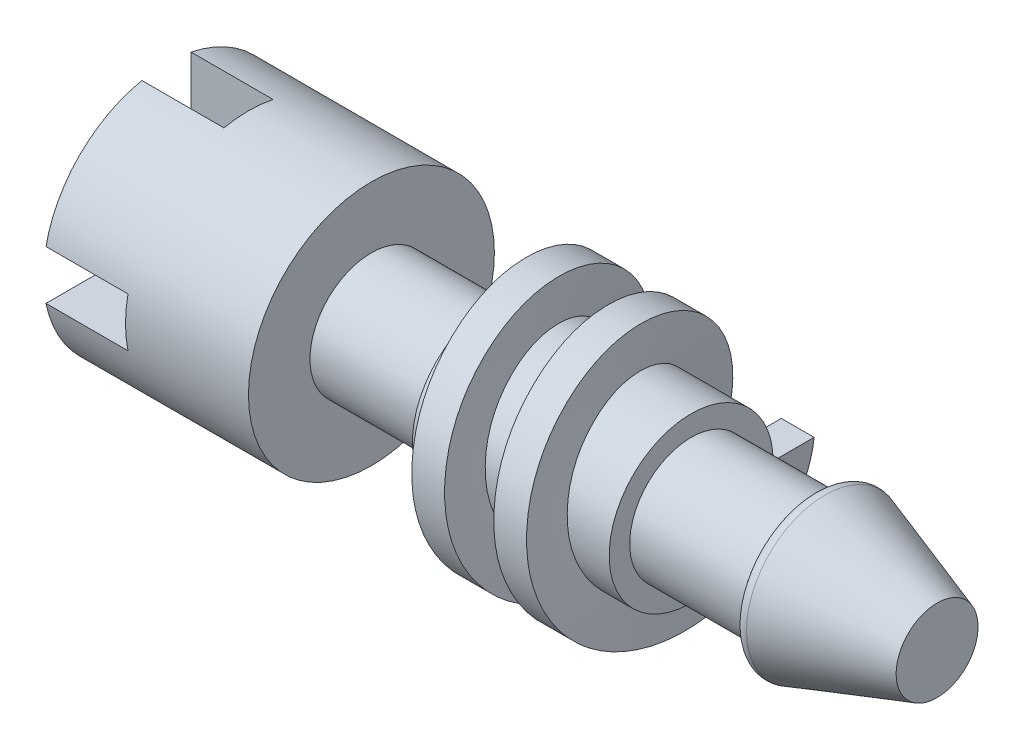
SolidWorks part; units mm, degrees
material "AISI 304"
ref_plane "Front Plane" through (0, 0, 0) normal (0, 0, 1) x (1, 0, 0)
ref_plane "Top Plane" through (0, 0, 0) normal (0, 1, 0) x (1, 0, 0)
ref_plane "Right Plane" through (0, 0, 0) normal (1, 0, 0) x (0, 0, -1)
sketch "Sketch1" plane through (0, 0, 0) normal (1, 0, 0) x (0, 0, -1)
  circle A0 centre (0, 0) radius 1.5
  circle A1 centre (0, 0) radius 1
  circle A2 centre (0, 0) radius 0.75
  dimension "D1" = 2
  dimension "D2" = 3
  dimension "D3" = 1.5
extrude "Boss-Extrude4" add sketch "Sketch1" along normal blind 1.5 contours A2
extrude "Boss-Extrude5" add sketch "Sketch1<6>" against normal blind 2.5 contours A0
sketch "Sketch1<6>" plane through (0, 0, 0) normal (1, 0, 0) x (0, 0, -1) same geometry as "Sketch1"
extrude "Boss-Extrude6" add sketch "Sketch1<7>" along normal blind 2.4 from surface contours A1 starting at face at (1.5, 0, -0.75)
sketch "Sketch1<7>" plane through (0, 0, 0) normal (1, 0, 0) x (0, 0, -1) same geometry as "Sketch1"
ref_plane "Plane2" through (1.75, 0, 0) normal (-1, 0, 0) x (0, 0, 1)
sketch "Sketch6" plane through (1.75, 0, 0) normal (-1, 0, 0) x (0, 0, 1)
  circle A0 centre (0, 0) radius 1.5
  dimension "D1" = 3
curve "Helix/Spiral2" pitch 1 height 2 radius 1.5 centre (1.75, 0, 0) axis (1, 0, 0) start towards (0, 0, 1)
sketch "Sketch7" plane through (0, 0, 0) normal (0, 1, 0) x (1, 0, 0)
  line L0 (3.9, 1) -> (1.5, 1) construction
  line L1 (1.5, 1.5) -> (1.9, 1.5)
  line L2 (1.5, 1.5) -> (1.5, 1)
  line L3 (1.5, 1) -> (1.9, 1)
  line L4 (1.9, 1.5) -> (1.9, 1)
  line L5 (0, -1.5) -> (0, 1.5) construction
  point P6 (1.7, 1.5)
  dimension "D1" = 0.4
  dimension "D2" = 0.5
  dimension "D3" = 1.7
sweep "Sweep2" add profiles "Sketch7" path "Helix/Spiral2"
extrude "Boss-Extrude7" add sketch "Sketch1<8>" along normal blind 1.5 from surface contours A2 starting at face at (3.9, 0, -1)
sketch "Sketch1<8>" plane through (0, 0, 0) normal (1, 0, 0) x (0, 0, -1) same geometry as "Sketch1"
sketch "Sketch8" plane through (-2.5, 0, 0) normal (-1, 0, 0) x (0, 0, 1)
  line L0 (0, 1.5) -> (0, -1.5) construction
  line L1 (-1.5, 0) -> (1.5, 0) construction
  line L2 (0.3, 1.4697) -> (0.3, 0.3)
  line L3 (-1.4697, 0.3) -> (-0.3, 0.3)
  line L4 (-0.3, 1.4697) -> (-0.3, 0.3)
  line L5 (-1.4697, -0.3) -> (-0.3, -0.3)
  line L6 (0.3, 0.3) -> (1.4697, 0.3)
  line L7 (-0.3, -0.3) -> (-0.3, -1.4697)
  line L8 (0.3, -0.3) -> (0.3, -1.4697)
  line L9 (0.3, -0.3) -> (1.4697, -0.3)
  circle A0 centre (0, 0) radius 1.5 construction
  arc A1 (-1.4697, 0.3) -> (-1.4697, -0.3) centre (0, 0) ccw
  arc A2 (0.3, 1.4697) -> (-0.3, 1.4697) centre (0, 0) ccw
  arc A3 (1.4697, -0.3) -> (1.4697, 0.3) centre (0, 0) ccw
  arc A4 (-0.3, -1.4697) -> (0.3, -1.4697) centre (0, 0) ccw
  dimension "D1" = 0.3
  dimension "D2" = 0.3
extrude "Cut-Extrude2" cut sketch "Sketch8" against normal blind 1
sketch "Sketch9" plane through (0, 0, 0) normal (0, 1, 0) x (1, 0, 0)
  line L0 (0, 0) -> (7.4883, 0) construction
  line L1 (5.4, 0) -> (5.4, 1)
  line L2 (5.4, -0.75) -> (5.4, 0.75) construction
  line L3 (5.4, 1) -> (6.9, 0.5)
  line L4 (6.9, 0.5) -> (6.9, 0)
  line L5 (5.4, 0) -> (6.9, 0)
  dimension "D1" = 1
  dimension "D2" = 1.5
  dimension "D3" = 0.5
revolve "Revolve2" add sketch "Sketch9" angle 360 about L0
fillet "Fillet2" radius 0.1 1 edges at (5.4, 0, 1)
